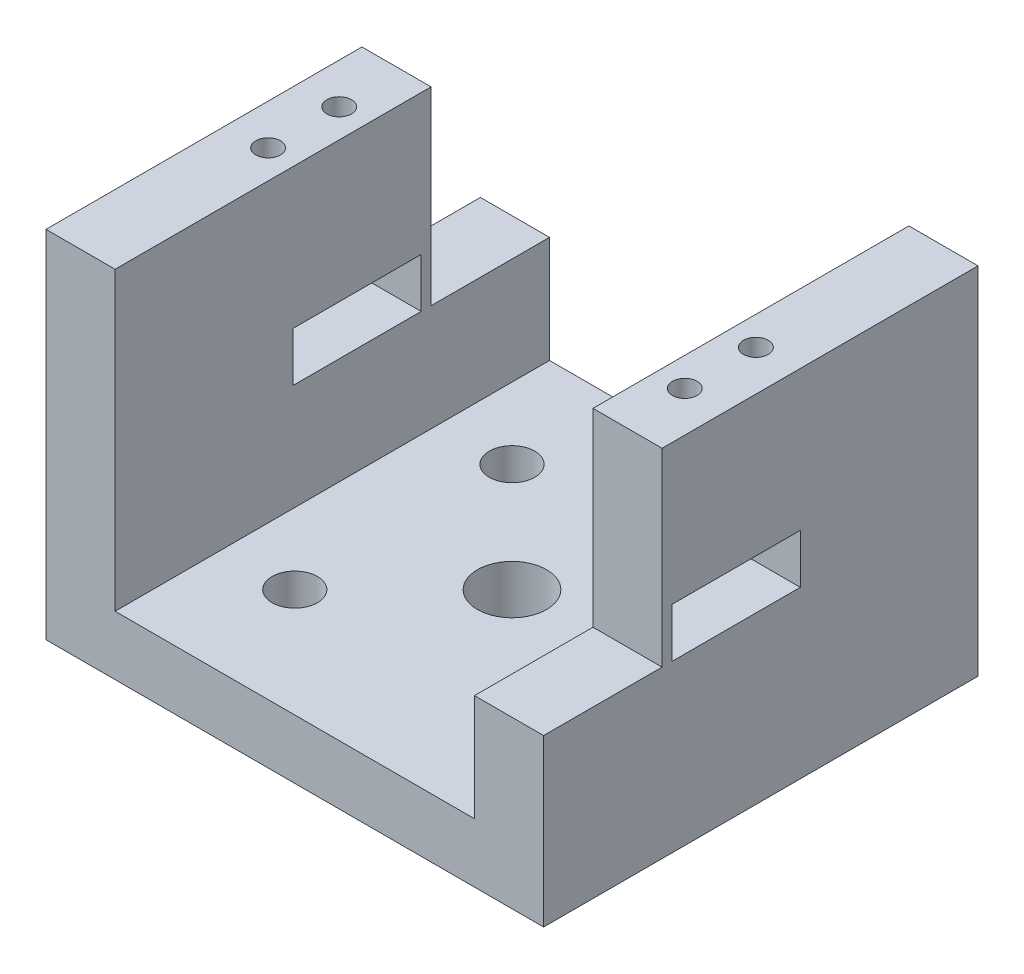
SolidWorks part; units mm, degrees
ref_plane "Front Plane" through (0, 0, 0) normal (0, 0, 1) x (1, 0, 0)
ref_plane "Top Plane" through (0, 0, 0) normal (0, 1, 0) x (1, 0, 0)
ref_plane "Right Plane" through (0, 0, 0) normal (1, 0, 0) x (0, 0, -1)
sketch "Sketch1" plane through (0, 0, 0) normal (0, 0, 1) x (1, 0, 0)
  line L0 (-18.2, 0) -> (18.2, 0)
  line L1 (18.2, 0) -> (18.2, 30)
  line L2 (18.2, 30) -> (25.2, 30)
  line L3 (25.2, 30) -> (25.2, -6)
  line L4 (25.2, -6) -> (-25.2, -6)
  line L5 (0, -6) -> (0, 0) construction
  line L6 (-25.2, 30) -> (-25.2, -6)
  line L7 (-18.2, 30) -> (-25.2, 30)
  line L8 (-18.2, 0) -> (-18.2, 30)
  dimension "D1" = 6
  dimension "D2" = 7
  dimension "D3" = 36.4
  dimension "D4" = 30
extrude "Boss-Extrude1" add sketch "Sketch1" along normal mid plane 44
sketch "Sketch2" plane through (0, 30, 0) normal (0, 1, 0) x (1, 0, 0)
  line L0 (-6.378, 0) -> (0, 0) construction
  line L1 (0, 0) -> (0, -10.2026) construction
  circle A0 centre (-21.1, -3.6) radius 1.25
  circle A1 centre (-21.1, 3.6) radius 1.25
  circle A2 centre (21.1, 3.6) radius 1.25
  circle A3 centre (21.1, -3.6) radius 1.25
  dimension "D1" = 42.2
  dimension "D2" = 7.2
  dimension "D3" = 2.5
extrude "Cut-Extrude1" cut sketch "Sketch2" against normal blind 16
sketch "Sketch3" plane through (25.2, 0, 0) normal (1, 0, 0) x (0, 0, -1)
  line L0 (-22, -6) -> (-22, 30) construction
  line L1 (-22, 15.8) -> (4, 15.8)
  line L2 (-22, 15.8) -> (-22, 10.8)
  line L3 (-22, 10.8) -> (4, 10.8)
  line L4 (4, 15.8) -> (4, 10.8)
  line L5 (-22, 30) -> (22, 30) construction
  line L7 (-10, 15.8) -> (-22, 15.8)
  line L8 (-10, 15.8) -> (-10, 30)
  line L9 (-10, 30) -> (-22, 30)
  line L10 (-22, 15.8) -> (-22, 30)
  line M6 (22, 30) -> (-22, 30)
  line M7 (-22, 30) -> (-22, -6)
  dimension "D1" = 5
  dimension "D2" = 26
  dimension "D3" = 14.2
  dimension "D4" = 12
extrude "Cut-Extrude2" cut sketch "Sketch3" against normal up to next contours L1 L8 M6 M7 | L4 L1 L3 M7 region at (25.2, 22.9, 16) region at (25.2, 13.3, 9)
ref_axis "Axis1" through (0, -7.8, 0) along (0, 1, 0)
sketch "Sketch4" plane through (0, 0, 10) normal (0, 0, 1) x (1, 0, 0)
  line L1 (18.2, 15.8) -> (25.2, 15.8)
  line L2 (18.2, 15.8) -> (18.2, 10.8)
  line L3 (18.2, 10.8) -> (25.2, 10.8)
  line L4 (25.2, 15.8) -> (25.2, 10.8)
extrude "Boss-Extrude2" add sketch "Sketch4" against normal blind 1
pattern_circular "CirPattern1" count 2 over 360 about axis through (0, -7.8, 0) along (0, 1, 0) of "Cut-Extrude2", "Boss-Extrude2"
sketch "Sketch5" plane through (0, 0, 0) normal (0, 1, 0) x (1, 0, 0)
  circle A0 centre (0, 0) radius 3.5
  circle A1 centre (-11, 11) radius 2.3
  circle A2 centre (11, 11) radius 2.3
  circle A3 centre (11, -11) radius 2.3
  circle A4 centre (-11, -11) radius 2.3
  point P13 (0, 0)
  dimension "D1" = 7
  dimension "D3" = 4.6
  dimension "D4" = 22
  dimension "D2" = 4
extrude "Cut-Extrude3" cut sketch "Sketch5" against normal up to next
